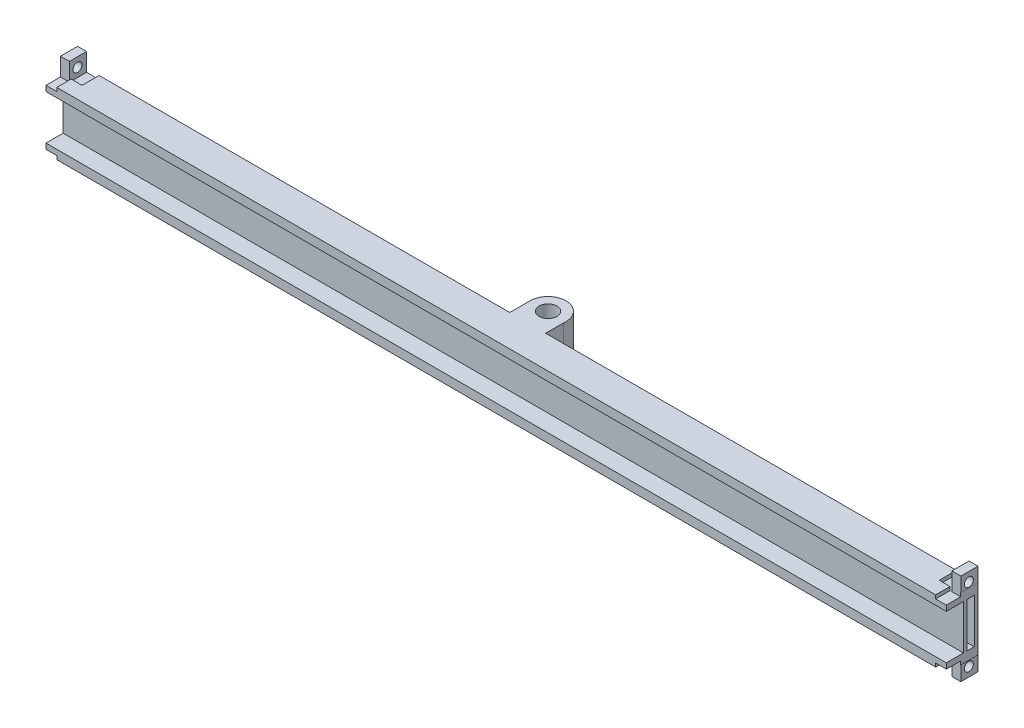
SolidWorks part; units mm, degrees
material "PLA"
ref_plane "Front Plane" through (0, 0, 0) normal (1, 0, 0) x (0, 1, 0)
ref_plane "Top Plane" through (0, 0, 0) normal (0, 0, 1) x (0, 1, 0)
ref_plane "Right Plane" through (0, 0, 0) normal (0, 1, 0) x (-1, 0, 0)
sketch "Sketch1" plane through (0, 0, 0) normal (1, 0, 0) x (0, 1, 0)
  line L16 (0, 4.7625) -> (-2.5, 4.7625)
  line L17 (0, 0) -> (12.3825, 0)
  line L18 (0, 0) -> (0, 4.7625)
  line L19 (0, 4.7625) -> (12.3825, 4.7625) construction
  line L20 (12.3825, 0) -> (12.3825, 4.7625)
  line L21 (-2.5, 4.7625) -> (-2.5, -4)
  line L22 (-2.5, -4) -> (14.8825, -4)
  line L23 (14.8825, -4) -> (14.8825, 4.7625)
  line L24 (12.3825, 4.7625) -> (14.8825, 4.7625)
  dimension "D1" = 4.7625
  dimension "D2" = 12.3825
  dimension "D3" = 2.5
extrude "Boss-Extrude1" add sketch "Sketch1" along normal blind 250
sketch "Sketch3" plane through (0, -2.5, 0) normal (0, -1, 0) x (1, 0, 0)
  line L0 (120.0194, -4) -> (129.9806, -4)
  line L1 (250, -4) -> (0, -4) construction
  line L2 (129.9806, -4) -> (129.9806, -9)
  line L3 (120.0194, -4) -> (120.0194, -9.6217)
  line L4 (0, 4.7625) -> (0, -4) construction
  arc A0 (120.0194, -9.6217) -> (129.9806, -9) centre (125.0194, -9.6217) ccw
  circle A1 centre (125.0194, -9.6217) radius 2.5
  point P5 (125, -4)
  dimension "D3" = 5
  dimension "D4" = 125
extrude "Boss-Extrude2" add sketch "Sketch3" against normal up to surface (17.3825 mm away) up to face at (125, 14.8825, 0.3813)
sketch "Sketch6" plane through (0, -2.5, 0) normal (0, -1, 0) x (1, 0, 0)
  line L0 (120.0194, -4) -> (0, -4) construction
  line L1 (117.5385, -4) -> (131.3691, -4)
  line L2 (117.5385, -4) -> (117.5385, -13.6365)
  line L3 (117.5385, -13.6365) -> (131.3691, -13.6365)
  line L4 (131.3691, -4) -> (131.3691, -13.6365)
extrude "Cut-Extrude2" [suppressed] cut sketch "Sketch6" against normal blind 5
sketch "Sketch7" plane through (0, 14.8825, 0) normal (0, 1, 0) x (-1, 0, 0)
  line L0 (-250, -4) -> (-129.9806, -4) construction
  line L1 (-136.5723, -4) -> (-116.3235, -4)
  line L2 (-136.5723, -4) -> (-136.5723, -14.7915)
  line L3 (-136.5723, -14.7915) -> (-116.3235, -14.7915)
  line L4 (-116.3235, -4) -> (-116.3235, -14.7915)
extrude "Cut-Extrude3" [suppressed] cut sketch "Sketch7" against normal blind 5
sketch "Sketch8" plane through (250, 0, 0) normal (1, 0, 0) x (0, 1, 0)
  line L0 (6.1913, 0) -> (6.1913, -4) construction
  line L5 (12.3825, 0) -> (0, 0) construction
  line L6 (14.8825, -4) -> (-2.5, -4) construction
  line L11 (0, -3) -> (12.3825, -3)
  line L12 (0, -3) -> (0, -1)
  line L13 (0, -1) -> (12.3825, -1)
  line L14 (12.3825, -3) -> (12.3825, -1)
  line L15 (0, -3) -> (12.3825, -1) construction
  line L16 (0, -1) -> (12.3825, -3) construction
  point P6 (6.1913, -2)
  dimension "D1" = 12.3825
extrude "Cut-Extrude4" cut sketch "Sketch8" against normal through all
sketch "Sketch9" plane through (0, 0, -4) normal (0, 0, -1) x (-1, 0, 0)
  line L0 (-117.5194, -2.5) -> (-117.5194, 14.8825) construction
  line L1 (-120.0194, -2.5) -> (0, -2.5) construction
  line L2 (-120.0194, 14.8825) -> (0, 14.8825) construction
  line L3 (-120.0194, 14.8825) -> (-120.0194, -2.5) construction
  line L4 (-116.5194, 12.3825) -> (-118.5194, 12.3825)
  line L5 (-116.5194, 12.3825) -> (-116.5194, 0)
  line L6 (-116.5194, 0) -> (-118.5194, 0)
  line L7 (-118.5194, 12.3825) -> (-118.5194, 0)
  line L8 (-116.5194, 12.3825) -> (-118.5194, 0) construction
  line L9 (-116.5194, 0) -> (-118.5194, 12.3825) construction
  point P6 (-117.5194, 6.1913)
  dimension "D3" = 2.5
  dimension "D1" = 12.3825
extrude "Cut-Extrude5" cut sketch "Sketch9" against normal up to next
ref_plane "Plane1" through (125.0194, 0, 0) normal (-1, 0, 0) x (0, 0, 1)
mirror "Mirror1" about plane through (125.0194, 0, 0) normal (-1, 0, 0) of "Cut-Extrude5"
sketch "Sketch10" plane through (0, 0, 4.7625) normal (0, 0, 1) x (1, 0, 0)
  line L1 (0, 14.8825) -> (2.5, 14.8825)
  line L2 (0, 14.8825) -> (0, 18.8912)
  line L3 (0, 18.8912) -> (2.5, 18.8912)
  line L4 (2.5, 14.8825) -> (2.5, 18.8912)
  line L5 (0, -2.5) -> (2.5, -2.5)
  line L6 (0, -2.5) -> (0, -6.5088)
  line L7 (0, -6.5088) -> (2.5, -6.5088)
  line L8 (2.5, -2.5) -> (2.5, -6.5088)
  dimension "D2" = 25.4
extrude "Boss-Extrude3" add sketch "Sketch10" against normal up to surface (8.7625 mm away) up to face at (117.5194, 6.1913, -4)
mirror "Mirror2" about plane through (125.0194, 0, 0) normal (-1, 0, 0) of "Boss-Extrude3"
sketch "Sketch11" plane through (250.0388, 0, 0) normal (1, 0, 0) x (0, 1, 0)
  circle A0 centre (16.3513, -1.46) radius 1.25 construction
  circle A1 centre (-3.9687, -1.46) radius 1.25 construction
  circle A2 centre (16.3513, -1.46) radius 1.25
  circle A3 centre (-3.9687, -1.46) radius 1.25
extrude "Cut-Extrude6" cut sketch "Sketch11" against normal up to surface (2.5 mm away) up to face at (247.5388, 16.8869, 0.3813)
mirror "Mirror3" about plane through (125.0194, 0, 0) normal (-1, 0, 0) of "Cut-Extrude6"
sketch "Sketch14" plane through (0, 0, 4.7625) normal (0, 0, 1) x (1, 0, 0)
  line L0 (0, 6.1912) -> (17.1619, 6.1912) construction
  line L1 (0, -6.5088) -> (3, -6.5088)
  line L2 (0, -6.5088) -> (0, -1.5088)
  line L3 (0, -1.5088) -> (3, -1.5088)
  line L4 (3, -6.5088) -> (3, -1.5088)
  line L5 (0, 12.3825) -> (0, 0) construction
  line L6 (0, 13.8912) -> (3, 13.8912)
  line L7 (3, 18.8912) -> (3, 13.8912)
  line L8 (0, 18.8912) -> (3, 18.8912)
  line L9 (0, 18.8912) -> (0, 13.8912)
  dimension "D2" = 3
extrude "Cut-Extrude7" cut sketch "Sketch14" against normal blind 4
mirror "Mirror4" about plane through (125.0194, 0, 0) normal (-1, 0, 0) of "Cut-Extrude7"
sketch "Sketch15" plane through (0, -2.5, 0) normal (0, -1, 0) x (-1, 0, 0)
  line L0 (-3, -0.7625) -> (-2.5, -0.7625) construction
  line L1 (-2.5, 4) -> (-6, 4)
  line L2 (-2.5, 4) -> (-2.5, -0.7625)
  line L3 (-2.5, -0.7625) -> (-6, -0.7625)
  line L4 (-6, 4) -> (-6, -0.7625)
  line L5 (0, 4) -> (0, -0.7625) construction
  dimension "D1" = 6
extrude "Cut-Extrude9" cut sketch "Sketch15" against normal blind 1 contours L4 L3 L2 L1
ref_plane "Plane3" through (0, 6.1913, 0) normal (0, 1, 0) x (1, 0, 0)
mirror "Mirror7" about plane through (0, 6.1913, 0) normal (0, 1, 0) of "Cut-Extrude9"
mirror "Mirror8" about plane through (125.0194, 0, 0) normal (-1, 0, 0) of "Mirror7"
equation "\"D1@Sketch1\"=\"ball_diameter\" * 0.25"
equation "\"D2@Sketch1\"=\"ball_diameter\" * 0.65"
equation "\"D3@Sketch1\"=\"wall_thickness\""
equation "\"D4@Sketch1\"=0.4cm"
equation "\"D1@Boss-Extrude1\"=\"track_length\""
equation "\"D2@Sketch3\"= \"axle\""
equation "\"ball_diameter\"= 0.75in"
equation "\"wall_thickness\" = 0.25cm"
equation "\"track_length\" = 25cm"
equation "\"axle\" = 5mm"
equation "\"D3@Sketch3\"=\"axle\" * 1"
equation "\"D4@Sketch3\"=\"track_length\" / 2"
equation "\"pillar_width\" = 2.75cm"
equation "\"D1@Sketch9\"=\"ball_diameter\" * 0.65"
equation "\"D1@Sketch8\"=\"ball_diameter\"*0.65"
equation "\"D1@Sketch10\"=\"wall_thickness\""
equation "\"D2@Sketch14\"=0.3"
